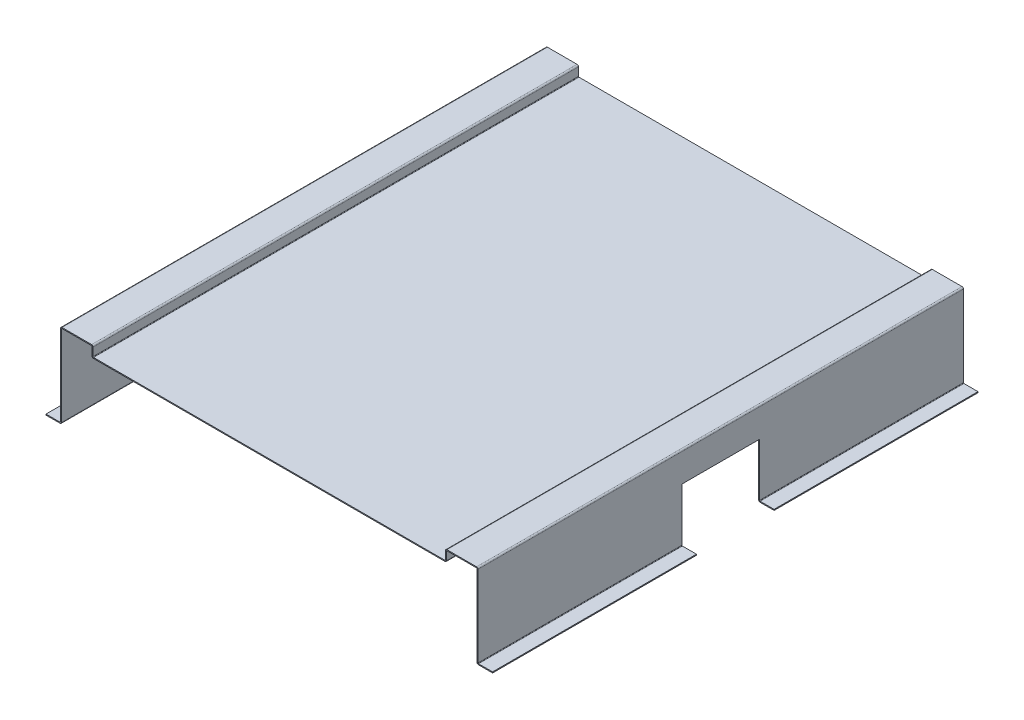
SolidWorks part; units mm, degrees
note: The reader was unsure of these and kept them because the rebuilt part matched: flange length of "边线-法兰1", "边线-法兰2", "边线-法兰3", "边线-法兰4".
ref_plane "前视基准面" through (0, 0, 0) normal (0, 0, 1) x (1, 0, 0)
ref_plane "上视基准面" through (0, 0, 0) normal (0, 1, 0) x (1, 0, 0)
ref_plane "右视基准面" through (0, 0, 0) normal (1, 0, 0) x (0, 0, -1)
sketch "草图1" plane through (0, 0, 0) normal (0, 1, 0) x (1, 0, 0)
  line L0 (0, 250) -> (0, -250)
  line L1 (-181, 250) -> (0, 250)
  line L2 (-181, 250) -> (-181, -250)
  line L3 (-181, -250) -> (0, -250)
  line L5 (0, 0) -> (197.7003, 0) construction
  point P0 (0, 0)
  dimension "D1" = 181
  dimension "D2" = 500
  dimension "D3" = 0
base flange "基体-法兰1" sketch "草图1" thickness 1 reverse thickness direction no parameters "D1"=0.5
edge flange "边线-法兰1" sketch "草图8" flange angle 90 flange length 10 flange position bend outside bend radius 0.5 thickness 1 relief rectangular parameters "D6"=10
sketch "草图8" plane through (-181, 0, 0) normal (-1, 0, 0) x (0, 0, 1)
  line L2 (-250, 0) -> (-250, 9)
  line L3 (-250, 9) -> (250, 9)
  line L4 (250, 9) -> (250, 0)
  line L7 (-250, 0) -> (250, 0) construction
  line L8 (-250, 0) -> (250, 0)
bend "边线折弯1" bend radius 0.5 bend angle 90 parameters "D5"=1
edge flange "边线-法兰2" sketch "草图11" flange angle 90 flange length 32 flange position bend outside bend radius 0.5 thickness 1 relief rectangular parameters "D6"=10
sketch "草图11" plane through (-182.5, 9, 0) normal (0, 1, 0) x (0, 0, -1)
  line L0 (-250, 0) -> (250, 0) construction
  line L1 (-250, 0) -> (250, 0)
  line L2 (-250, 0) -> (-250, 31)
  line L3 (-250, 31) -> (250, 31)
  line L4 (250, 31) -> (250, 0)
bend "边线折弯2" bend radius 0.5 bend angle 90 parameters "D5"=2
edge flange "边线-法兰3" sketch "草图14" flange angle 90 flange length 85 flange position bend outside bend radius 0.5 thickness 1 relief rectangular parameters "D6"=10
sketch "草图14" plane through (-213.5, 9.5, 0) normal (1, 0, 0) x (0, 0, 1)
  line L2 (-250, 0) -> (-250, 84)
  line L3 (-250, 84) -> (250, 84)
  line L4 (250, 84) -> (250, 0)
  line L5 (250, 0) -> (-250, 0) construction
  line L6 (250, 0) -> (-250, 0)
bend "边线折弯3" bend radius 0.5 bend angle 90 parameters "D5"=3
edge flange "边线-法兰4" sketch "草图17" flange angle 90 flange length 16 flange position bend outside bend radius 0.5 thickness 1 relief rectangular parameters "D6"=10
sketch "草图17" plane through (-215, -74.5, 0) normal (0, -1, 0) x (0, 0, 1)
  line L0 (250, 0) -> (-250, 0) construction
  line L1 (250, 0) -> (-250, 0)
  line L2 (-250, 0) -> (-250, 15)
  line L3 (-250, 15) -> (250, 15)
  line L4 (250, 15) -> (250, 0)
bend "边线折弯4" bend radius 0.5 bend angle 90 parameters "D5"=4
sketch "草图18" plane through (-230, 0, 0) normal (-1, 0, 0) x (0, 0, 1)
  line L0 (-250, 10.5) -> (250, 10.5) construction
  line L1 (-40, -20) -> (40, -20)
  line L2 (-40, -20) -> (-40, -91.4474)
  line L3 (-40, -91.4474) -> (40, -91.4474)
  line L4 (40, -20) -> (40, -91.4474)
  line L5 (-40, -20) -> (40, -91.4474) construction
  line L6 (-40, -91.4474) -> (40, -20) construction
  line L7 (0, 0) -> (0, -13.3259) construction
  point P0 (0, -55.7237)
  point P11 (0, -20)
  dimension "D1" = 30.5
  dimension "D2" = 80
  dimension "D3" = 0
extrude "切除-拉伸1" cut sketch "草图18" against normal blind 100 normal cut yes
mirror "镜向1" about plane through (0, -1, -250) normal (1, 0, 0) of bodies 111
bend "镜向折弯1" bend radius 0.5 bend angle 90 parameters "D5"=5
bend "镜向折弯2" bend radius 0.5 bend angle 90 parameters "D5"=6
bend "镜向折弯3" bend radius 0.5 bend angle 90 parameters "D5"=7
bend "镜向折弯4" bend radius 0.5 bend angle 90 parameters "D5"=8
sketch "折弯-线1" plane through (0, 0, 0) normal (0, 1, 0) x (1, 0, 0)
sketch "边界框1" plane through (0, 0, 0) normal (0, 1, 0) x (1, 0, 0)
sheet metal parameters "钣金6" thickness 1 parameters "D1"=0.5
flat pattern "平板型式6" [suppressed]
sketch "折弯-线2" plane through (0, 0, 0) normal (0, 1, 0) x (1, 0, 0)
sketch "边界框2" [suppressed] plane through (0, 0, 0) normal (0, 1, 0) x (1, 0, 0)
sheet metal parameters "钣金7" thickness 1 parameters "D1"=0.5
flat pattern "平板型式6" [suppressed]
sketch "折弯-线2" plane through (0, 0, 0) normal (0, 1, 0) x (1, 0, 0)
sketch "边界框2" [suppressed] plane through (0, 0, 0) normal (0, 1, 0) x (1, 0, 0)
bend of the flat pattern "展平-<边线折弯1>1"
sheet metal parameters "钣金8" thickness 1 parameters "D1"=0.5
flat pattern "平板型式6" [suppressed]
sketch "折弯-线2" plane through (0, 0, 0) normal (0, 1, 0) x (1, 0, 0)
sketch "边界框2" [suppressed] plane through (0, 0, 0) normal (0, 1, 0) x (1, 0, 0)
bend of the flat pattern "展平-<边线折弯1>1"
bend of the flat pattern "展平-<边线折弯2>1"
sheet metal parameters "钣金9" thickness 1 parameters "D1"=0.5
flat pattern "平板型式6" [suppressed]
sketch "折弯-线2" plane through (0, 0, 0) normal (0, 1, 0) x (1, 0, 0)
sketch "边界框2" [suppressed] plane through (0, 0, 0) normal (0, 1, 0) x (1, 0, 0)
bend of the flat pattern "展平-<边线折弯1>1"
bend of the flat pattern "展平-<边线折弯2>1"
bend of the flat pattern "展平-<边线折弯3>1"
sheet metal parameters "钣金10" thickness 1 parameters "D1"=0.5
flat pattern "平板型式6" [suppressed]
sketch "折弯-线2" plane through (0, 0, 0) normal (0, 1, 0) x (1, 0, 0)
sketch "边界框2" [suppressed] plane through (0, 0, 0) normal (0, 1, 0) x (1, 0, 0)
bend of the flat pattern "展平-<边线折弯1>1"
bend of the flat pattern "展平-<边线折弯2>1"
bend of the flat pattern "展平-<边线折弯3>1"
bend of the flat pattern "展平-<边线折弯4>1"
sheet metal parameters "钣金11" thickness 1 parameters "D1"=0.5
flat pattern "平板型式6" [suppressed]
sketch "折弯-线2" plane through (0, 0, 0) normal (0, 1, 0) x (1, 0, 0)
sketch "边界框2" [suppressed] plane through (0, 0, 0) normal (0, 1, 0) x (1, 0, 0)
bend of the flat pattern "展平-<边线折弯1>1"
bend of the flat pattern "展平-<边线折弯2>1"
bend of the flat pattern "展平-<边线折弯3>1"
bend of the flat pattern "展平-<边线折弯4>1"
sheet metal parameters "钣金12" thickness 1 parameters "D1"=0.5
flat pattern "平板型式12" [suppressed]
sketch "折弯-线3" plane through (0, 0, 0) normal (0, 1, 0) x (1, 0, 0)
sketch "边界框3" [suppressed] plane through (0, 0, 0) normal (0, 1, 0) x (1, 0, 0)
bend of the flat pattern "展平-<边线折弯1>2"
bend of the flat pattern "展平-<边线折弯2>2"
bend of the flat pattern "展平-<边线折弯3>2"
bend of the flat pattern "展平-<边线折弯4>2"
bend of the flat pattern "展平-<镜向折弯1>1"
bend of the flat pattern "展平-<镜向折弯2>1"
bend of the flat pattern "展平-<镜向折弯3>1"
bend of the flat pattern "展平-<镜向折弯4>1"
